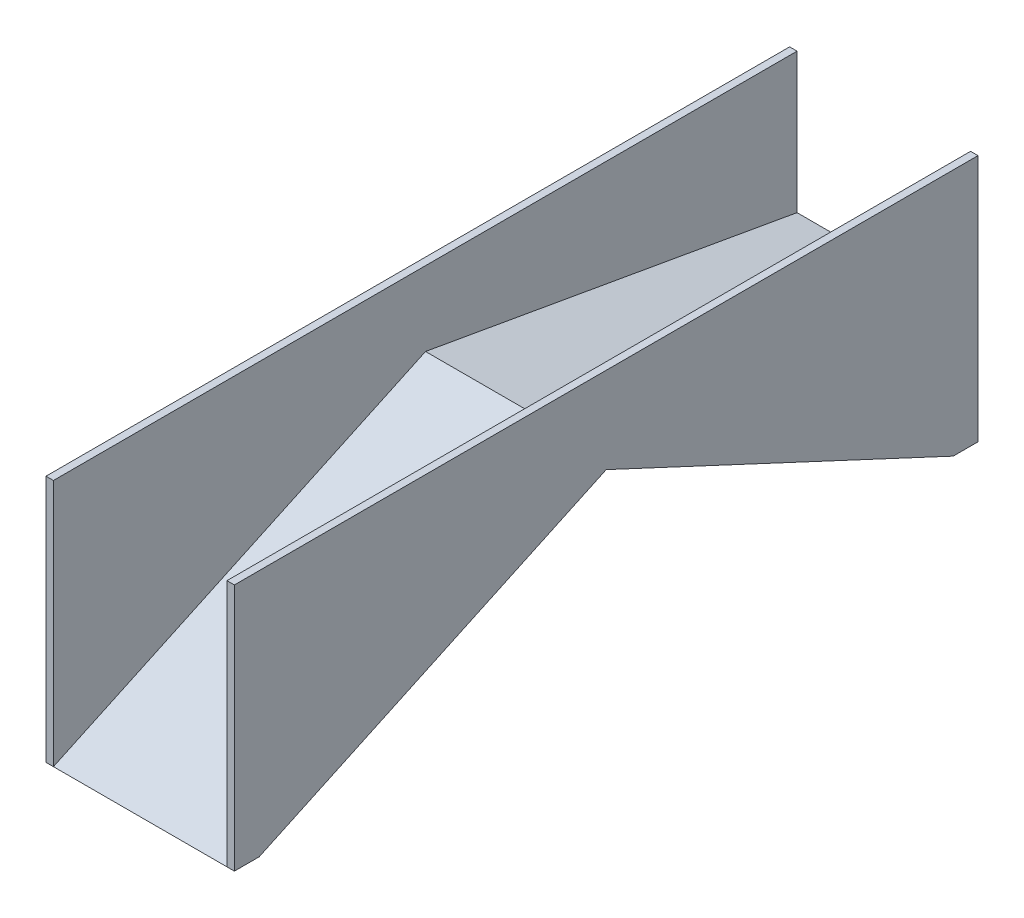
SolidWorks part; units mm, degrees
ref_plane "Front Plane" through (0, 0, 0) normal (0, 0, 1) x (1, 0, 0)
ref_plane "Top Plane" through (0, 0, 0) normal (0, 1, 0) x (1, 0, 0)
ref_plane "Right Plane" through (0, 0, 0) normal (1, 0, 0) x (0, 0, -1)
sketch "Sketch1" plane through (0, 0, 0) normal (0, 1, 0) x (1, 0, 0)
  line L1 (-46.7318, -161.724) -> (23.2682, -161.724)
  line L2 (-46.7318, -161.724) -> (-46.7318, 138.276)
  line L3 (-46.7318, 138.276) -> (23.2682, 138.276)
  line L4 (23.2682, -161.724) -> (23.2682, 138.276)
  line L5 (23.2682, -161.724) -> (26.2682, -161.724)
  line L6 (23.2682, -161.724) -> (23.2682, 138.276)
  line L7 (23.2682, 138.276) -> (26.2682, 138.276)
  line L8 (26.2682, -161.724) -> (26.2682, 138.276)
  line L9 (-46.7318, 138.276) -> (-49.7318, 138.276)
  line L10 (-46.7318, 138.276) -> (-46.7318, -161.724)
  line L11 (-46.7318, -161.724) -> (-49.7318, -161.724)
  line L12 (-49.7318, 138.276) -> (-49.7318, -161.724)
  dimension "D1" = 300
  dimension "D2" = 70
  dimension "D3" = 3
  dimension "D4" = 3
extrude "Boss-Extrude1" add sketch "Sketch1" along normal blind 70 contours L1 L4 L3 L2 region at (-11.7318, 0, 11.724)
extrude "Boss-Extrude2" add sketch "Sketch1<4>" along normal blind 100 contours L9 L12 L11 L2 | L5 L8 L7 L4 region at (-48.2318, 0, 11.724) region at (24.7682, 0, 11.724)
sketch "Sketch1<4>" plane through (0, 0, 0) normal (0, 1, 0) x (1, 0, 0) same geometry as "Sketch1"
sketch "Sketch2" plane through (-46.7318, 0, 0) normal (-1, 0, 0) x (0, 0, 1)
  line L0 (11.6085, 70) -> (161.724, 0)
  line L2 (11.6085, 70) -> (11.6085, 0)
  line L4 (-138.276, 0) -> (161.724, 0) construction
  line L5 (11.6085, 0) -> (161.724, 0)
  line L6 (11.6085, 70) -> (161.724, 70)
  line L7 (161.724, 70) -> (161.724, 0)
  point P0 (11.6085, 70)
  dimension "D1" = 25
extrude "Cut-Extrude1" cut sketch "Sketch2" against normal up to surface (70 mm away) contours L0 | L7 L0 region at (-46.7318, 46.6667, 111.6855) up to face at (23.2682, 85, 11.724)
sketch "Sketch3" plane through (-46.7318, 0, 0) normal (-1, 0, 0) x (0, 0, 1)
  line L0 (11.6085, 70) -> (-138.276, 70)
  line L1 (-138.276, 70) -> (-138.276, 43.5713)
  line L2 (-138.276, 70) -> (-138.276, 5) construction
  line L3 (-138.276, 43.5713) -> (11.6085, 70)
  dimension "D1" = 10
extrude "Cut-Extrude2" cut sketch "Sketch3" against normal up to surface (70 mm away) up to face at (23.2682, 68, 11.7009)
sketch "Sketch8" plane through (26.2682, 0, 0) normal (1, 0, 0) x (0, 0, -1)
  line L0 (-151.724, 0) -> (-11.724, 65.2831)
  line L1 (-161.724, 0) -> (138.276, 0) construction
  line L2 (-151.724, 0) -> (-11.724, 0)
  line L3 (-11.724, 0) -> (-11.724, 65.2831) construction
  line L4 (-11.724, 65.2831) -> (128.276, 0)
  line L5 (128.276, 0) -> (-11.724, 0)
  dimension "D1" = 10
  dimension "D2" = 25
  dimension "D3" = 10
  dimension "D4" = 140
extrude "Cut-Extrude3" cut sketch "Sketch8" against normal through all
sketch "Sketch10" plane through (0, 0, 0) normal (0, -1, 0) x (1, 0, 0)
  line L0 (-11.7318, -128.276) -> (-11.7318, -138.276) construction
  line L1 (-36.7318, -128.276) -> (13.2682, -128.276)
  line L2 (-36.7318, -128.276) -> (-36.7318, -58.276)
  line L3 (-36.7318, -58.276) -> (13.2682, -58.276)
  line L4 (13.2682, -128.276) -> (13.2682, -58.276)
  line L5 (-49.7318, -138.276) -> (26.2682, -138.276) construction
  dimension "D1" = 10
  dimension "D2" = 50
  dimension "D3" = 70
extrude "Cut-Extrude4" cut sketch "Sketch10" against normal blind 30
